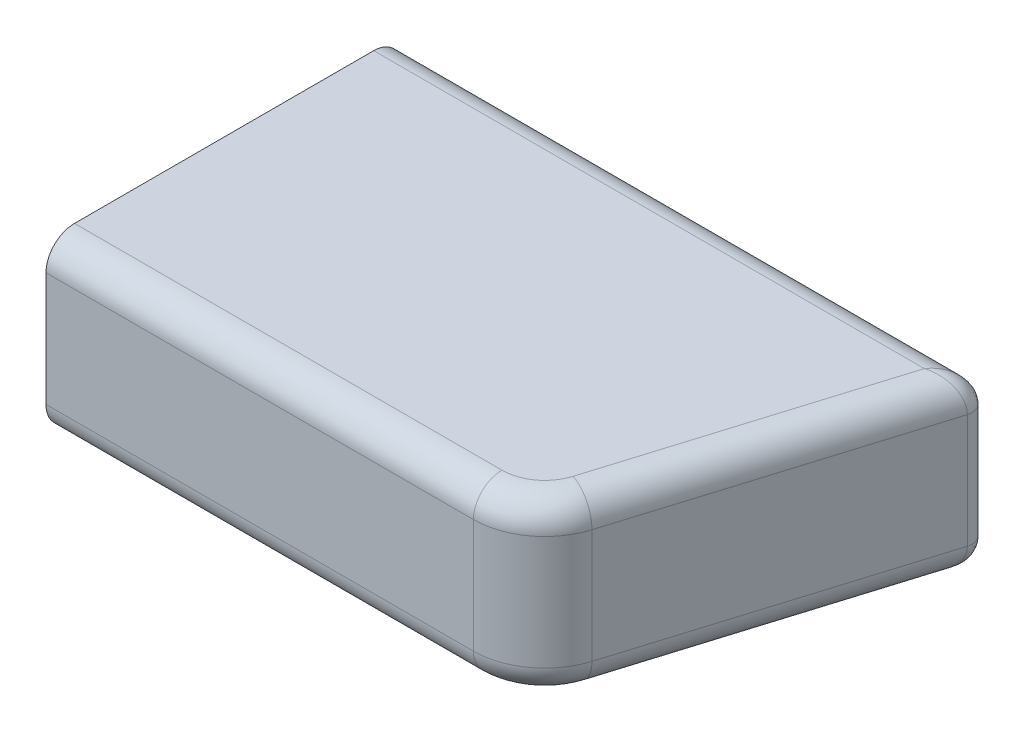
SolidWorks part; units mm, degrees
ref_plane "Alzado" through (0, 0, 0) normal (0, 0, 1) x (1, 0, 0)
ref_plane "Planta" through (0, 0, 0) normal (0, 1, 0) x (1, 0, 0)
ref_plane "Vista lateral" through (0, 0, 0) normal (1, 0, 0) x (0, 0, -1)
sketch "Sketch1" plane through (0, 0, 0) normal (0, 1, 0) x (1, 0, 0)
  line L0 (-7.6665, 16.8831) -> (-7.6665, -8.1169)
  line L1 (-7.6665, -8.1169) -> (22.3335, -8.1169)
  line L2 (27.1145, -4.5806) -> (33.2897, 15.5904)
  line L3 (32.3335, 16.8831) -> (-7.6665, 16.8831)
  arc A0 (22.3335, -8.1169) -> (27.1145, -4.5806) centre (22.3335, -3.1169) ccw
  arc A1 (33.2897, 15.5904) -> (32.3335, 16.8831) centre (32.3335, 15.8831) ccw
  dimension "D1" = 5
  dimension "D2" = 1
  dimension "D3" = 40
  dimension "D4" = 30
  dimension "D5" = 25
extrude "Boss-Extrude1" add sketch "Sketch1" along normal blind 12
fillet "Fillet1" radius 2 10 edges at (7.3335, 0, 8.1169) (25.3069, 0, 7.1367) (12.3335, 0, -16.8831) (33.1375, 0, -16.4778) (7.3335, 12, 8.1169) (25.3069, 12, 7.1367) (12.3335, 12, -16.8831) (33.1375, 12, -16.4778) (30.2021, 0, -5.5049) (30.2021, 12, -5.5049)
